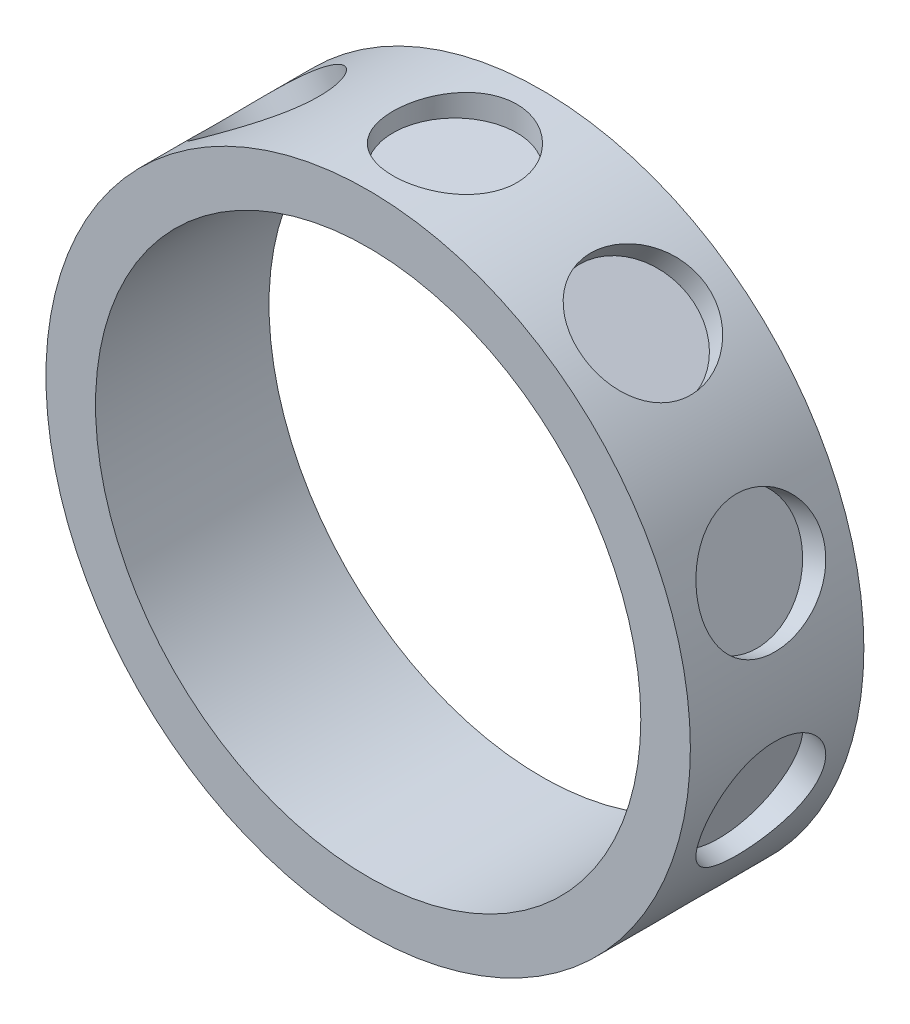
SolidWorks part; units mm, degrees
ref_plane "Top Plane" through (0, 0, 0) normal (0, 0, 1) x (1, 0, 0)
ref_plane "Right Plane" through (0, 0, 0) normal (0, 1, 0) x (1, 0, 0)
ref_plane "Front Plane" through (0, 0, 0) normal (1, 0, 0) x (0, 0, -1)
ref_axis "x-axis" through (-88.99, 0, 0) along (1, 0, 0)
ref_axis "y-axis" through (0, -55, 0) along (0, 1, 0)
ref_axis "z-axis" through (0, 0, 55) along (0, 0, -1)
sketch "Sketch1" plane through (0, 0, 0) normal (0, 0, 1) x (1, 0, 0)
  circle A0 centre (0, 0) radius 11
  circle A1 centre (0, 0) radius 13
  dimension "D1" = 22
  dimension "D2" = 2
extrude "Boss-Extrude1" add sketch "Sketch1" along normal mid plane 7
ref_plane "Plane1" through (0, 13, 0) normal (0, 1, 0) x (1, 0, 0)
sketch "Sketch2" plane through (0, 13, 0) normal (0, 1, 0) x (1, 0, 0)
  circle A0 centre (0, 0) radius 2.5
extrude "Cut-Extrude3" cut sketch "Sketch2" against normal blind 1
pattern_circular "CirPattern1" count 10 over 360 about axis through (0, 0, 3.5) along (0, 0, -1) of "Cut-Extrude3" reverse direction yes
